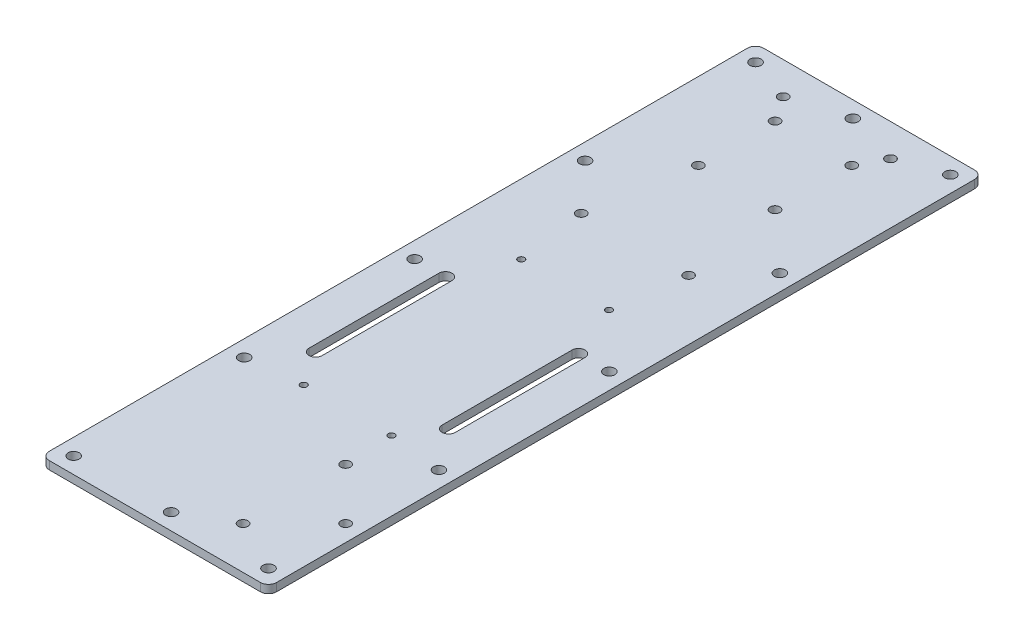
SolidWorks part; units mm, degrees
ref_plane "Front Plane" through (0, 0, 0) normal (0, 0, 1) x (1, 0, 0)
ref_plane "Top Plane" through (0, 0, 0) normal (0, 1, 0) x (1, 0, 0)
ref_plane "Right Plane" through (0, 0, 0) normal (1, 0, 0) x (0, 0, -1)
sketch "Sketch2" plane through (0, 0, 0) normal (0, 1, 0) x (1, 0, 0)
  line L0 (-44.45, 0) -> (44.45, 0) construction
  line L1 (-41.275, 139.7) -> (41.275, 139.7)
  line L2 (-44.45, 136.525) -> (-44.45, -136.525)
  line L3 (-41.275, -139.7) -> (41.275, -139.7)
  line L4 (44.45, 136.525) -> (44.45, -136.525)
  line L5 (0, 139.7) -> (0, -139.7) construction
  arc A0 (-44.45, -136.525) -> (-41.275, -139.7) centre (-41.275, -136.525) ccw
  arc A1 (41.275, -139.7) -> (44.45, -136.525) centre (41.275, -136.525) ccw
  arc A2 (41.275, 139.7) -> (44.45, 136.525) centre (41.275, 136.525) cw
  arc A3 (-41.275, 139.7) -> (-44.45, 136.525) centre (-41.275, 136.525) ccw
  point P8 (0, 0)
  point P13 (-44.45, -139.7)
  point P16 (44.45, -139.7)
  point P21 (-44.45, 139.7)
  dimension "D3" = 3.175
  dimension "D1" = 279.4
  dimension "D2" = 88.9
extrude "Plate Thickness" add sketch "Sketch2" along normal blind 3.175 contours L2 A0 L3 A1 L4 A2 L1 A3
sketch "Sketch3" plane through (0, 3.175, 0) normal (0, 1, 0) x (1, 0, 0)
  line L0 (-44.45, 136.525) -> (-44.45, -136.525) construction
  line L1 (-41.275, 139.7) -> (41.275, 139.7) construction
  line L4 (0, 139.7) -> (0, -139.7) construction
  line L5 (-41.275, -139.7) -> (41.275, -139.7) construction
  circle A0 centre (-38.1, 133.35) radius 2.159
  circle A1 centre (-38.1, 66.675) radius 2.159
  circle A2 centre (-38.1, -66.675) radius 2.159
  circle A3 centre (-38.1, -133.35) radius 2.159
  circle A4 centre (38.1, -133.35) radius 2.159
  circle A5 centre (38.1, -66.675) radius 2.159
  circle A6 centre (38.1, 66.675) radius 2.159
  circle A7 centre (38.1, 133.35) radius 2.159
  circle A8 centre (0, 133.35) radius 2.159
  circle A9 centre (0, -133.35) radius 2.159
  circle A10 centre (-38.1, 0) radius 2.159
  circle A11 centre (38.1, 0) radius 2.159
  dimension "D1" = 4.318
  dimension "D4" = 4.318
  dimension "D2" = 6.35
  dimension "D3" = 6.35
  dimension "D5" = 66.675
  dimension "D6" = 6.35
  dimension "D7" = 66.675
extrude "Mounting holes" cut sketch "Sketch3" against normal through all
sketch "Sketch4" plane through (0, 3.175, 0) normal (0, 1, 0) x (1, 0, 0)
  line L0 (-21.0058, 48.0812) -> (21.0058, 48.0812) construction
  line L1 (0, 0) -> (0, 139.7) construction
  line L4 (-41.275, 139.7) -> (41.275, 139.7) construction
  circle A0 centre (-21.0058, 127.0752) radius 1.905
  circle A1 centre (-21.0058, 48.0812) radius 1.905
  circle A2 centre (21.0058, 48.0812) radius 1.905
  circle A3 centre (21.0058, 127.0752) radius 1.905
  point P8 (21.9632, 114.5384)
  point P10 (-20.3567, 115.3106)
  point P13 (0, 48.0812)
  point P15 (0, 69.85)
  point P16 (0, 139.7)
  point P17 (0, 69.85)
  point P18 (0, 69.85)
  point P19 (20.5431, 127.0752)
  dimension "D1" = 3.81
  dimension "D2" = 78.994
  dimension "D3" = 42.0116
extrude "Jetson Holes (w/ mount)" cut sketch "Sketch4" against normal through all
sketch "Sketch5" plane through (0, 3.175, 0) normal (0, 1, 0) x (1, 0, 0)
  circle A1 centre (-14.3419, 117.2351) radius 1.905
  circle A3 centre (15.6555, 117.2351) radius 1.905
  circle A4 centre (15.6555, 87.2377) radius 1.905
  circle A5 centre (-14.3419, 87.2377) radius 1.905
  dimension "D1" = 3.81
  dimension "D2" = 29.9974
  dimension "D3" = 29.9974
extrude "PDB holes" cut sketch "Sketch5" against normal through all
sketch "Sketch6" plane through (0, 3.175, 0) normal (0, 1, 0) x (1, 0, 0)
  circle A6 centre (38.0032, -103.0828) radius 1.905
  circle A7 centre (17.9372, -83.0168) radius 1.905
  circle A8 centre (17.9372, -123.1488) radius 1.905
  point P0 (38.0032, -103.0828)
  point P12 (31.3131, -31.4557)
  dimension "D5" = 3.81
  dimension "D6" = 40.132
  dimension "D7" = 20.066
  dimension "D8" = 20.066
extrude "Lidar Holes" cut sketch "Sketch6" against normal through all
sketch "Sketch7" plane through (0, 3.175, 0) normal (0, 1, 0) x (1, 0, 0)
  line L0 (0, 139.7) -> (0, -139.7) construction
  line L1 (-41.275, 139.7) -> (41.275, 139.7) construction
  line L2 (-41.275, -139.7) -> (41.275, -139.7) construction
  line L3 (17.145, 20.7699) -> (-17.145, 20.7699) construction
  circle A0 centre (-17.145, 20.7699) radius 1.27
  circle A1 centre (-17.145, -64.3201) radius 1.27
  circle A2 centre (17.145, -64.3201) radius 1.27
  circle A3 centre (17.145, 20.7699) radius 1.27
  point P14 (0, 20.7699)
  point P15 (-17.145, 22.6774)
  point P16 (-17.145, 20.7699)
  dimension "D1" = 2.54
  dimension "D2" = 85.09
  dimension "D3" = 34.29
extrude "PixHawk Holes" cut sketch "Sketch7" against normal through all
sketch "Sketch8" plane through (0, 3.175, 0) normal (0, 1, 0) x (1, 0, 0)
  line L0 (0, 139.7) -> (0, -115.5095) construction
  line L1 (-41.275, 139.7) -> (41.275, 139.7) construction
  line L2 (-26.035, -0.006) -> (-26.035, -50.806) construction
  line L3 (-23.495, -0.006) -> (-23.495, -50.806)
  line L4 (-28.575, -0.006) -> (-28.575, -50.806)
  line L5 (26.035, -0.006) -> (26.035, -50.806) construction
  line L6 (23.495, -0.006) -> (23.495, -50.806)
  line L7 (28.575, -0.006) -> (28.575, -50.806)
  arc A0 (-23.495, -0.006) -> (-28.575, -0.006) centre (-26.035, -0.006) ccw
  arc A1 (-28.575, -50.806) -> (-23.495, -50.806) centre (-26.035, -50.806) ccw
  arc A2 (23.495, -0.006) -> (28.575, -0.006) centre (26.035, -0.006) cw
  arc A3 (28.575, -50.806) -> (23.495, -50.806) centre (26.035, -50.806) cw
  point P7 (-26.035, -25.406)
  point P14 (26.035, -25.406)
  dimension "D1" = 50.8
  dimension "D2" = 5.08
  dimension "D3" = 26.035
extrude "Battery Holes" cut sketch "Sketch8" against normal through all
